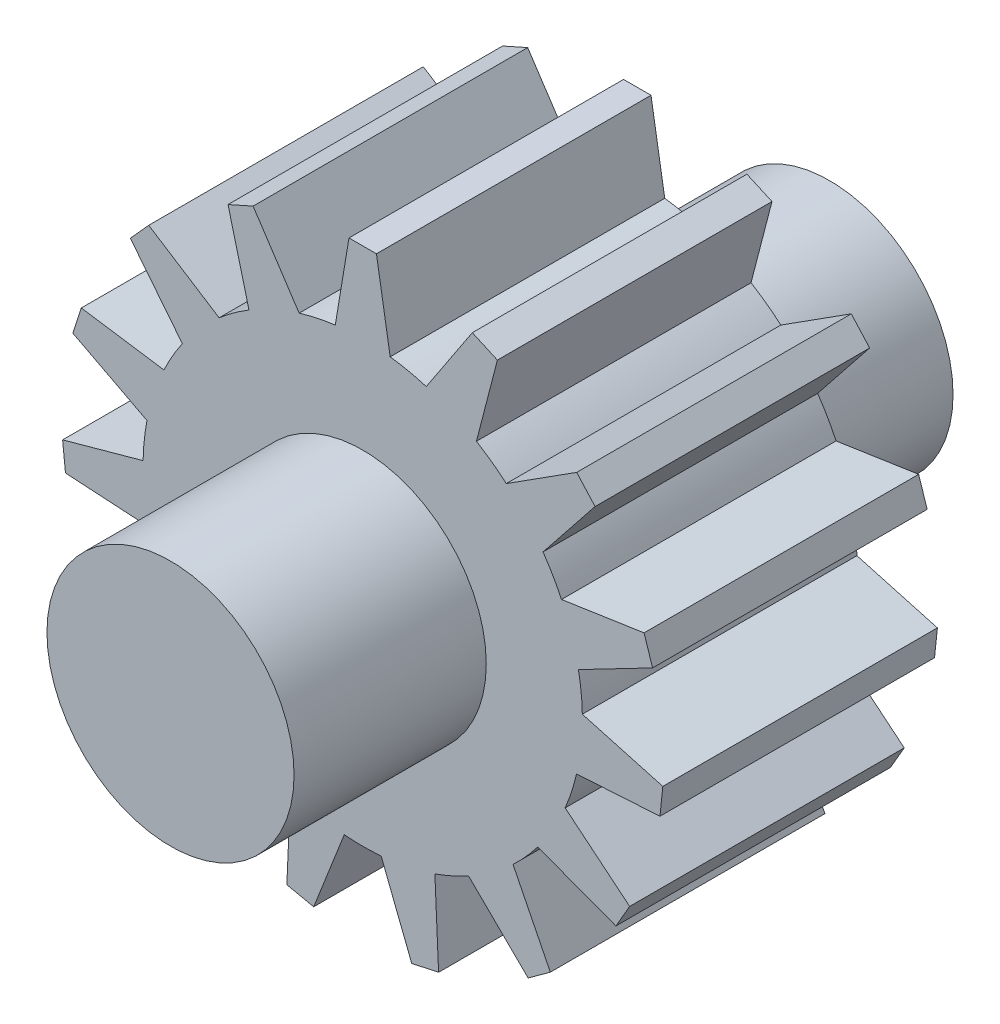
SolidWorks part; units mm, degrees
ref_plane "Front Plane" through (0, 0, 0) normal (0, 0, 1) x (1, 0, 0)
ref_plane "Top Plane" through (0, 0, 0) normal (0, 1, 0) x (1, 0, 0)
ref_plane "Right Plane" through (0, 0, 0) normal (1, 0, 0) x (0, 0, -1)
sketch "Sketch1" plane through (0, 0, 0) normal (0, 0, 1) x (1, 0, 0)
  line L0 (0, 131.0364) -> (0, -129.5668) construction
  line L1 (-243.9481, 0) -> (265.9916, 0) construction
  circle A0 centre (0, 0) radius 8
extrude "Boss-Extrude1" add sketch "Sketch1" along normal blind 10
sketch "Sketch2" plane through (0, 0, 10) normal (0, 0, 1) x (1, 0, 0)
  line L0 (0, 12.6562) -> (0, -11.3341) construction
  line L1 (-14.4402, 0) -> (12.5048, 0) construction
  line L2 (-1, 7.9373) -> (-0.5, 10.9373)
  line L3 (-0.5, 10.9373) -> (0.5, 10.9373)
  line L4 (0.5, 10.9373) -> (1, 7.9373)
  line L5 (1, 7.9373) -> (-1, 7.9373)
  line L6 (2.3148, 7.6578) -> (3.9918, 10.195)
  line L7 (4.9054, 9.7883) -> (4.1419, 6.8443)
  line L8 (3.9918, 10.195) -> (4.9054, 9.7883)
  line L9 (4.1419, 6.8443) -> (2.3148, 7.6578)
  line L10 (5.2294, 6.0542) -> (7.7934, 7.69)
  line L11 (8.4625, 6.9469) -> (6.5677, 4.5679)
  line L12 (7.7934, 7.69) -> (8.4625, 6.9469)
  line L13 (6.5677, 4.5679) -> (5.2294, 6.0542)
  line L14 (7.2398, 3.4038) -> (10.2474, 3.8553)
  line L15 (10.5565, 2.9043) -> (7.8578, 1.5017)
  line L16 (10.2474, 3.8553) -> (10.5565, 2.9043)
  line L17 (7.8578, 1.5017) -> (7.2398, 3.4038)
  line L18 (7.9983, 0.1649) -> (10.9296, -0.646)
  line L19 (10.8251, -1.6405) -> (7.7892, -1.8242)
  line L20 (10.9296, -0.646) -> (10.8251, -1.6405)
  line L21 (7.7892, -1.8242) -> (7.9983, 0.1649)
  line L22 (7.3739, -3.1026) -> (9.7219, -5.0356)
  line L23 (9.2219, -5.9016) -> (6.3739, -4.8347)
  line L24 (9.7219, -5.0356) -> (9.2219, -5.9016)
  line L25 (6.3739, -4.8347) -> (7.3739, -3.1026)
  line L26 (5.4744, -5.8336) -> (6.8333, -8.5545)
  line L27 (6.0242, -9.1423) -> (3.8564, -7.0092)
  line L28 (6.8333, -8.5545) -> (6.0242, -9.1423)
  line L29 (3.8564, -7.0092) -> (5.4744, -5.8336)
  line L30 (2.6284, -7.5559) -> (2.7631, -10.5943)
  line L31 (1.7849, -10.8022) -> (0.6721, -7.9717)
  line L32 (2.7631, -10.5943) -> (1.7849, -10.8022)
  line L33 (0.6721, -7.9717) -> (2.6284, -7.5559)
  line L34 (-0.6721, -7.9717) -> (-1.7849, -10.8022)
  line L35 (-2.7631, -10.5943) -> (-2.6284, -7.5559)
  line L36 (-1.7849, -10.8022) -> (-2.7631, -10.5943)
  line L37 (-2.6284, -7.5559) -> (-0.6721, -7.9717)
  line L38 (-3.8564, -7.0092) -> (-6.0242, -9.1423)
  line L39 (-6.8333, -8.5545) -> (-5.4744, -5.8336)
  line L40 (-6.0242, -9.1423) -> (-6.8333, -8.5545)
  line L41 (-5.4744, -5.8336) -> (-3.8564, -7.0092)
  line L42 (-6.3739, -4.8347) -> (-9.2219, -5.9016)
  line L43 (-9.7219, -5.0356) -> (-7.3739, -3.1026)
  line L44 (-9.2219, -5.9016) -> (-9.7219, -5.0356)
  line L45 (-7.3739, -3.1026) -> (-6.3739, -4.8347)
  line L46 (-7.7892, -1.8242) -> (-10.8251, -1.6405)
  line L47 (-10.9296, -0.646) -> (-7.9983, 0.1649)
  line L48 (-10.8251, -1.6405) -> (-10.9296, -0.646)
  line L49 (-7.9983, 0.1649) -> (-7.7892, -1.8242)
  line L50 (-7.8578, 1.5017) -> (-10.5565, 2.9043)
  line L51 (-10.2474, 3.8553) -> (-7.2398, 3.4038)
  line L52 (-10.5565, 2.9043) -> (-10.2474, 3.8553)
  line L53 (-7.2398, 3.4038) -> (-7.8578, 1.5017)
  line L54 (-6.5677, 4.5679) -> (-8.4625, 6.9469)
  line L55 (-7.7934, 7.69) -> (-5.2294, 6.0542)
  line L56 (-8.4625, 6.9469) -> (-7.7934, 7.69)
  line L57 (-5.2294, 6.0542) -> (-6.5677, 4.5679)
  line L58 (-4.1419, 6.8443) -> (-4.9054, 9.7883)
  line L59 (-3.9918, 10.195) -> (-2.3148, 7.6578)
  line L60 (-4.9054, 9.7883) -> (-3.9918, 10.195)
  line L61 (-2.3148, 7.6578) -> (-4.1419, 6.8443)
  circle A0 centre (0, 0) radius 8 construction
  point P70 (0, 0)
  dimension "D1" = 3
  dimension "D2" = 1
  dimension "D3" = 2
extrude "Boss-Extrude2" add sketch "Sketch2" against normal up to surface (10 mm away) up to face at (8, 0, 0)
sketch "Sketch3" plane through (0, 0, 10) normal (0, 0, 1) x (1, 0, 0)
  line L0 (-14.6039, 0) -> (13.7779, 0) construction
  line L1 (0, 11.7804) -> (0, -11.5462) construction
  circle A0 centre (0, 0) radius 4.5
  dimension "D1" = 9
extrude "Boss-Extrude3" add sketch "Sketch3" along normal blind 7
extrude "Boss-Extrude4" add sketch "Sketch3<2>" along normal blind 7
sketch "Sketch3<2>" plane through (0, 0, 10) normal (0, 0, 1) x (1, 0, 0) same geometry as "Sketch3"
sketch "Sketch4" plane through (0, 0, 0) normal (0, 0, -1) x (-1, 0, 0)
  line L0 (0, 11.6482) -> (0, -11.3149) construction
  line L1 (-12.3241, 0) -> (12.258, 0) construction
  circle A0 centre (0, 0) radius 4.5
  dimension "D1" = 9
extrude "Boss-Extrude5" add sketch "Sketch4" along normal blind 7
sketch "Sketch5" plane through (0, 0, -7) normal (0, 0, -1) x (-1, 0, 0)
  line L0 (0, 11.6813) -> (0, -9.9272) construction
  line L1 (-11.432, 0) -> (11.4651, 0) construction
  circle A0 centre (0, 0) radius 3
  circle A1 centre (0, 0) radius 4.5 construction
  dimension "D1" = 1.5
extrude "Cut-Extrude9" cut sketch "Sketch5" against normal up to surface (7 mm away) up to face at (0, 0, 0)
